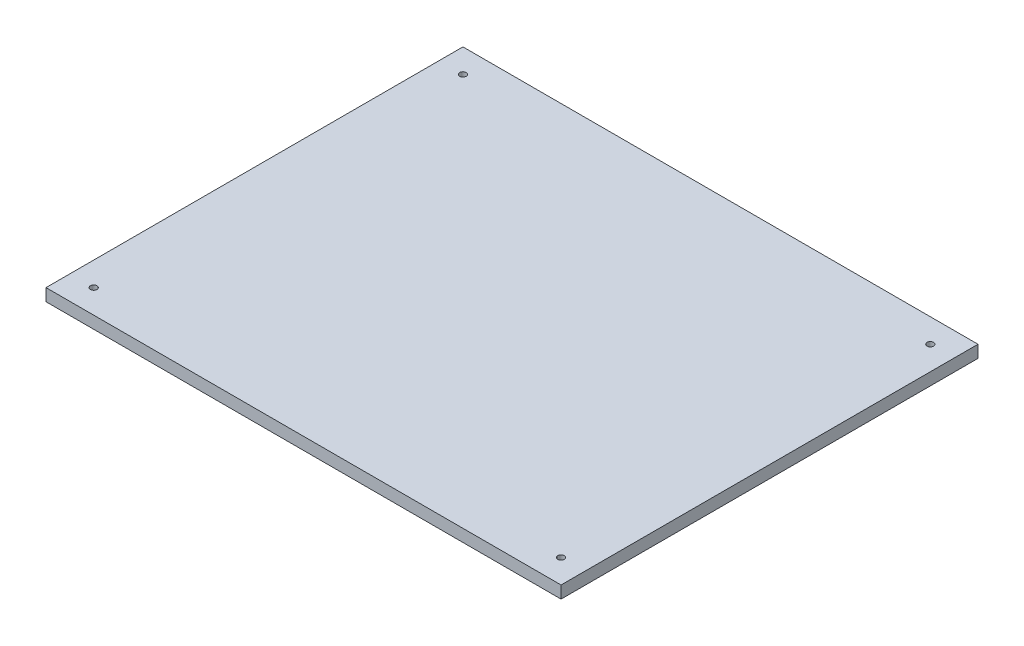
SolidWorks part; units mm, degrees
material "Acrylic (Medium-high impact)"
ref_plane "Front Plane" through (0, 0, 0) normal (0, 0, 1) x (1, 0, 0)
ref_plane "Top Plane" through (0, 0, 0) normal (0, 1, 0) x (1, 0, 0)
ref_plane "Right Plane" through (0, 0, 0) normal (1, 0, 0) x (0, 0, -1)
sketch "Sketch1" plane through (0, 0, 0) normal (0, 1, 0) x (1, 0, 0)
  line L1 (-133.35, 107.95) -> (133.35, 107.95)
  line L2 (-133.35, 107.95) -> (-133.35, -107.95)
  line L3 (-133.35, -107.95) -> (133.35, -107.95)
  line L4 (133.35, 107.95) -> (133.35, -107.95)
  line L5 (-133.35, 107.95) -> (133.35, -107.95) construction
  line L6 (-133.35, -107.95) -> (133.35, 107.95) construction
  point P0 (0, 0)
  dimension "D1" = 215.9
  dimension "D2" = 266.7
extrude "Boss-Extrude1" add sketch "Sketch1" along normal blind 6.35
hole_wizard "M3 Clearance Hole1" positions "Sketch2" profile "Sketch3" hole size "M3" standard "ANSI Metric" end condition through all
sketch "Sketch2" plane through (0, 6.35, 0) normal (0, 1, 0) x (1, 0, 0)
  line L0 (-133.35, -107.95) -> (133.35, -107.95) construction
  line L1 (133.35, -107.95) -> (133.35, 107.95) construction
  line L2 (133.35, 107.95) -> (-133.35, 107.95) construction
  line L3 (-133.35, 107.95) -> (-133.35, -107.95) construction
  point P0 (121.0056, -95.6056)
  point P2 (-121.0056, -95.6056)
  point P4 (-121.0056, 95.6056)
  point P6 (121.0056, 95.6056)
  dimension "D1" = 12.3444
  dimension "D2" = 12.3444
  dimension "D3" = 12.3444
  dimension "D4" = 12.3444
sketch "Sketch3" plane through (121.0056, 6.35, 95.6056) normal (1, 0, 0) x (0, 0, 1)
  line L0 (0, 0) -> (0, 6.35)
  line L1 (0, 6.35) -> (1.7, 6.35)
  line L2 (1.7, 6.35) -> (1.7, 0)
  line L5 (1.7, 0) -> (0, 0)
  line L11 (0, -6.35) -> (0, 107.95) construction
  dimension "Thru Hole Dia." = 3.4
  dimension "Thru Hole Depth" = 6.35
